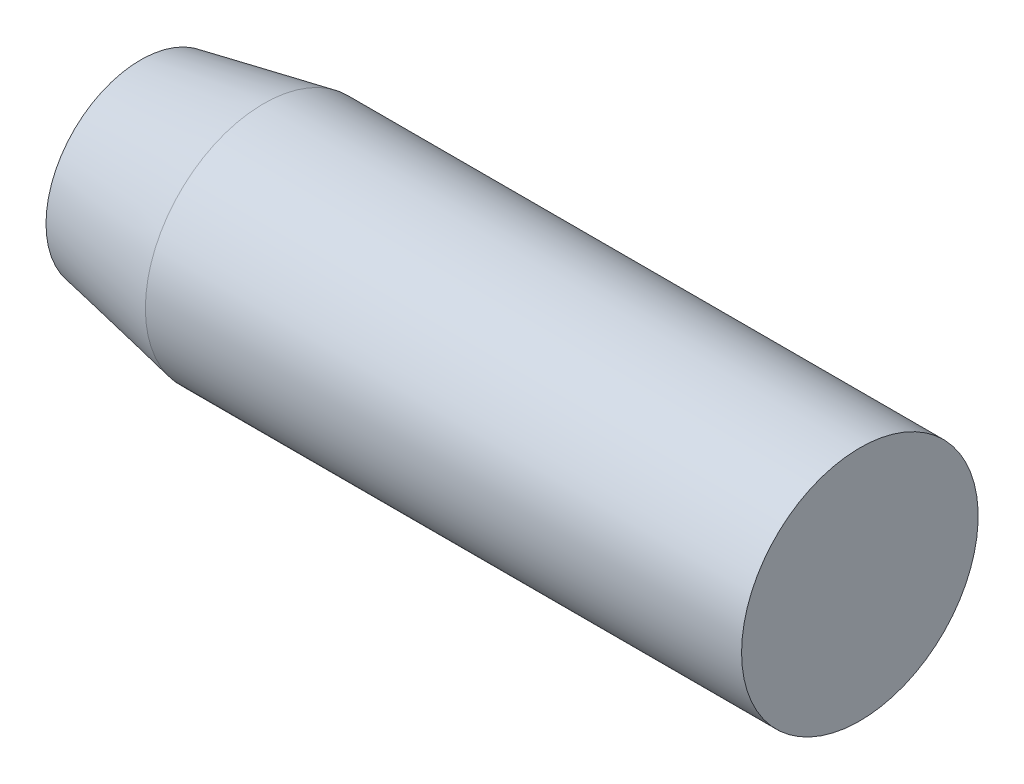
SolidWorks part; units mm, degrees
ref_plane "Front Plane" through (0, 0, 0) normal (0, 0, 1) x (1, 0, 0)
ref_plane "Top Plane" through (0, 0, 0) normal (0, 1, 0) x (1, 0, 0)
ref_plane "Right Plane" through (0, 0, 0) normal (1, 0, 0) x (0, 0, -1)
sketch "Sketch1" plane through (0, 0, 0) normal (0, 1, 0) x (1, 0, 0)
  line L0 (0, 0) -> (38, 0)
  line L1 (38, 0) -> (38, 6.25)
  line L2 (38, 6.25) -> (6.5, 6.25)
  line L3 (6.5, 6.25) -> (0, 5)
  line L4 (0, 5) -> (0, 0)
  line L5 (-19.0752, 0) -> (56.1168, 0) construction
  dimension "D1" = 6.25
  dimension "D2" = 5
  dimension "D3" = 6.5
  dimension "D4" = 38
revolve "Revolve1" add sketch "Sketch1" angle 360 about L0
ref_axis "Axis1" through (70.2533, 0, 0) along (-1, 0, 0)
sketch "Sketch2" plane through (38, 0, 0) normal (1, 0, 0) x (0, 0, -1)
  point P0 (0, 0)
